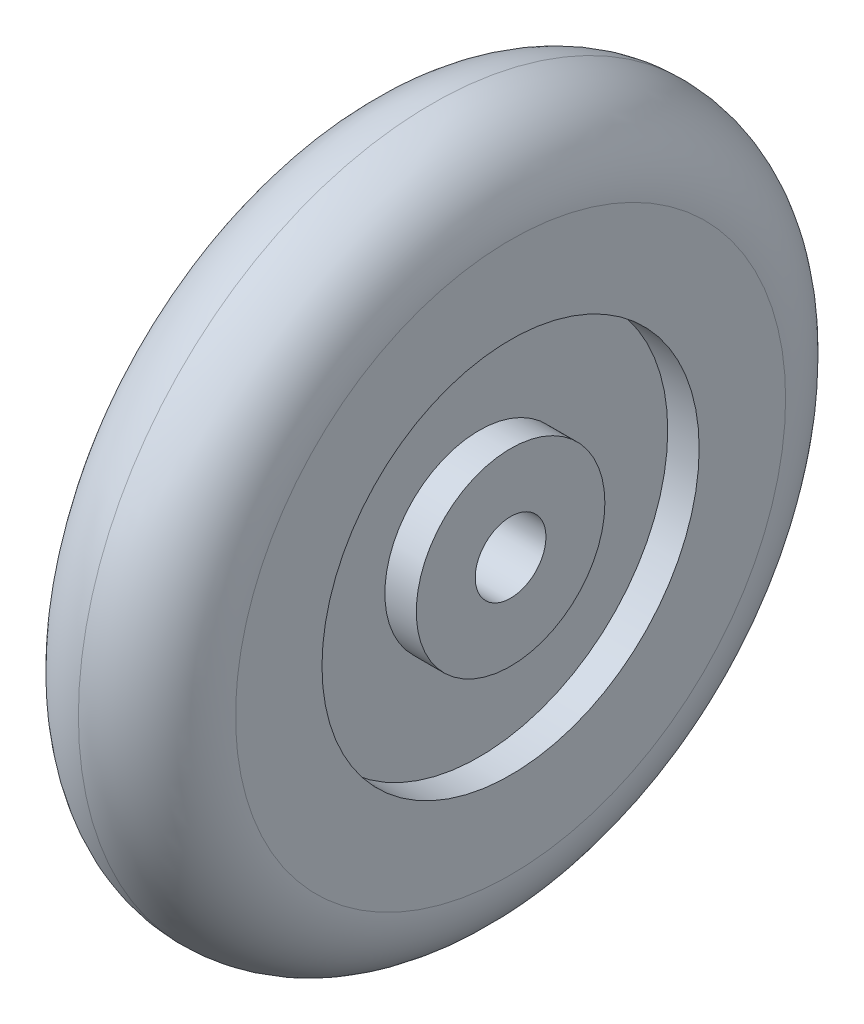
SolidWorks part; units mm, degrees
material "Oak"
ref_plane "Front" through (0, 0, 0) normal (0, 0, 1) x (1, 0, 0)
ref_plane "Top" through (0, 0, 0) normal (0, 1, 0) x (1, 0, 0)
ref_plane "Right" through (0, 0, 0) normal (1, 0, 0) x (0, 0, -1)
sketch "Sketch2" plane through (0, 0, 0) normal (1, 0, 0) x (0, 0, -1)
  circle A0 centre (0, 0) radius 22.5
  dimension "D1" = 45
extrude "Boss-Extrude1" add sketch "Sketch2" along normal mid plane 10
fillet "Fillet1" radius 5 2 edges at (-5, 0, -22.5) (5, 0, -22.5)
sketch "Sketch3" plane through (5, 0, 0) normal (1, 0, 0) x (0, 0, -1)
  circle A0 centre (0, 0) radius 6
  circle A1 centre (0, 0) radius 12
  dimension "D1" = 12
  dimension "D2" = 24
extrude "Cut-Extrude1" cut sketch "Sketch3" against normal blind 2
mirror "Mirror1" about plane through (0, 0, 0) normal (1, 0, 0) of "Cut-Extrude1"
sketch "Sketch4" plane through (5, 0, 0) normal (1, 0, 0) x (0, 0, -1)
  circle A0 centre (0, 0) radius 2.25
  dimension "D1" = 4.5
extrude "Cut-Extrude2" cut sketch "Sketch4" against normal through all
